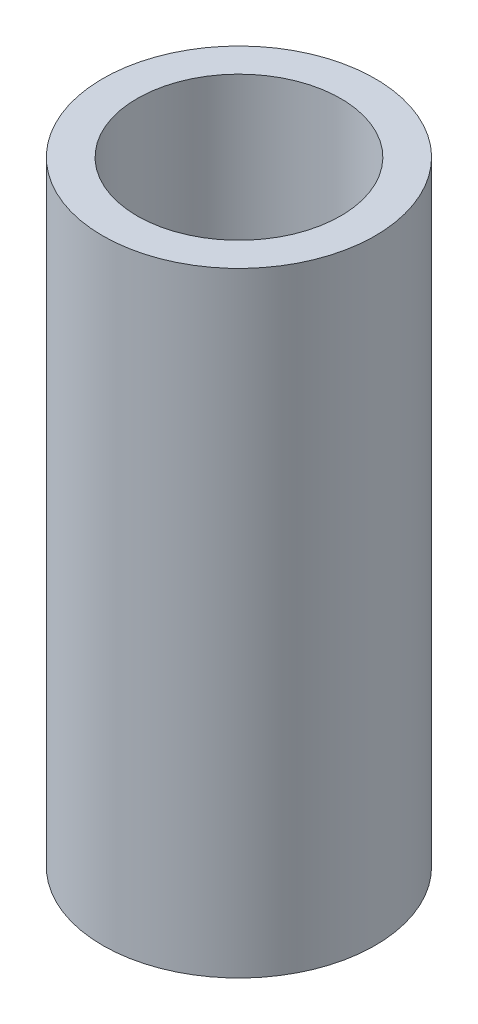
SolidWorks part; units mm, degrees
ref_plane "Front Plane" through (0, 0, 0) normal (0, 0, 1) x (1, 0, 0)
ref_plane "Top Plane" through (0, 0, 0) normal (0, 1, 0) x (1, 0, 0)
ref_plane "Right Plane" through (0, 0, 0) normal (1, 0, 0) x (0, 0, -1)
sketch "Sketch1" plane through (0, 0, 0) normal (0, 1, 0) x (1, 0, 0)
  circle A0 centre (0, 0) radius 15
  dimension "SLEEVE_OD" = 30
extrude "Boss-Extrude1" add sketch "Sketch1" along normal blind 67.6745
sketch "Sketch2" plane through (0, 0, 0) normal (0, 1, 0) x (1, 0, 0)
  circle A0 centre (0, 0) radius 11.2065
  dimension "BORE_D" = 22.4131
extrude "Cut-Extrude1" cut sketch "Sketch2" along normal through all
chamfer "Chamfer1" distance 2.8429 angle 35.248 rebuild error yes
